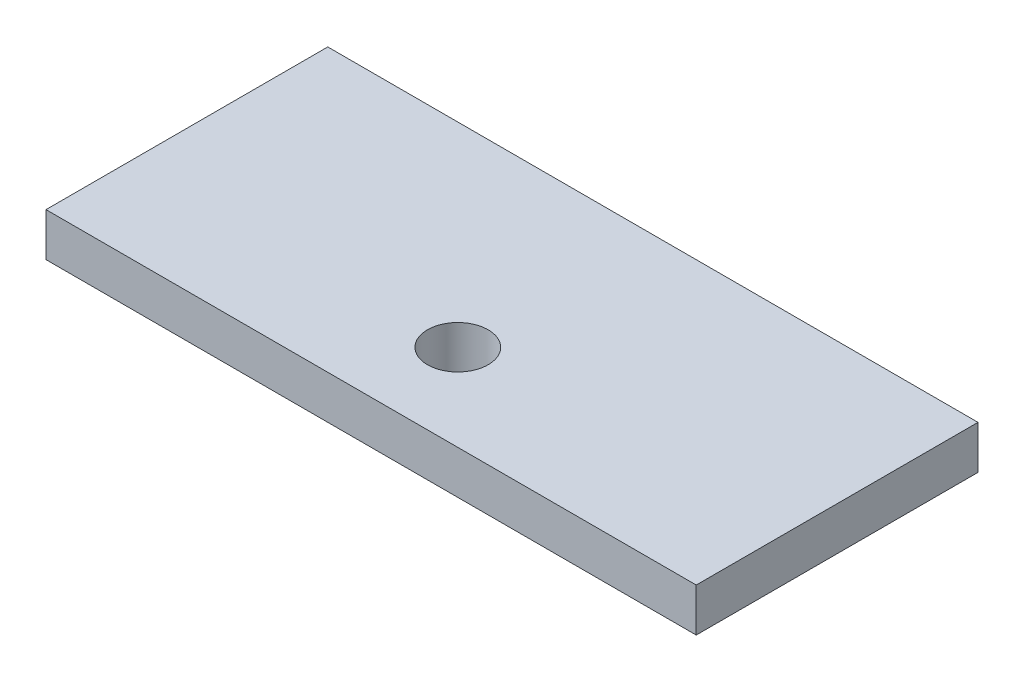
SolidWorks part; units mm, degrees
ref_plane "Front Plane" through (0, 0, 0) normal (0, 0, 1) x (1, 0, 0)
ref_plane "Top Plane" through (0, 0, 0) normal (0, 1, 0) x (1, 0, 0)
ref_plane "Right Plane" through (0, 0, 0) normal (1, 0, 0) x (0, 0, -1)
sketch "Sketch1" plane through (0, 0, 0) normal (0, 1, 0) x (1, 0, 0)
  line L1 (-75, -32.5) -> (75, -32.5)
  line L2 (-75, -32.5) -> (-75, 32.5)
  line L3 (-75, 32.5) -> (75, 32.5)
  line L4 (75, -32.5) -> (75, 32.5)
  line L5 (-75, -32.5) -> (75, 32.5) construction
  line L6 (-75, 32.5) -> (75, -32.5) construction
  point P0 (0, 0)
  dimension "D1" = 150
  dimension "D2" = 65
extrude "Boss-Extrude1" add sketch "Sketch1" along normal blind 10
sketch "Sketch2" plane through (0, 0, 0) normal (0, 1, 0) x (1, 0, 0)
  line L0 (0, 0) -> (0, -46.7949) construction
  line L1 (-75, -32.5) -> (75, -32.5) construction
  circle A0 centre (0, -12.5) radius 7
  dimension "D1" = 14
  dimension "D2" = 20
extrude "Cut-Extrude2" cut sketch "Sketch2" against normal through all and the other way through all
